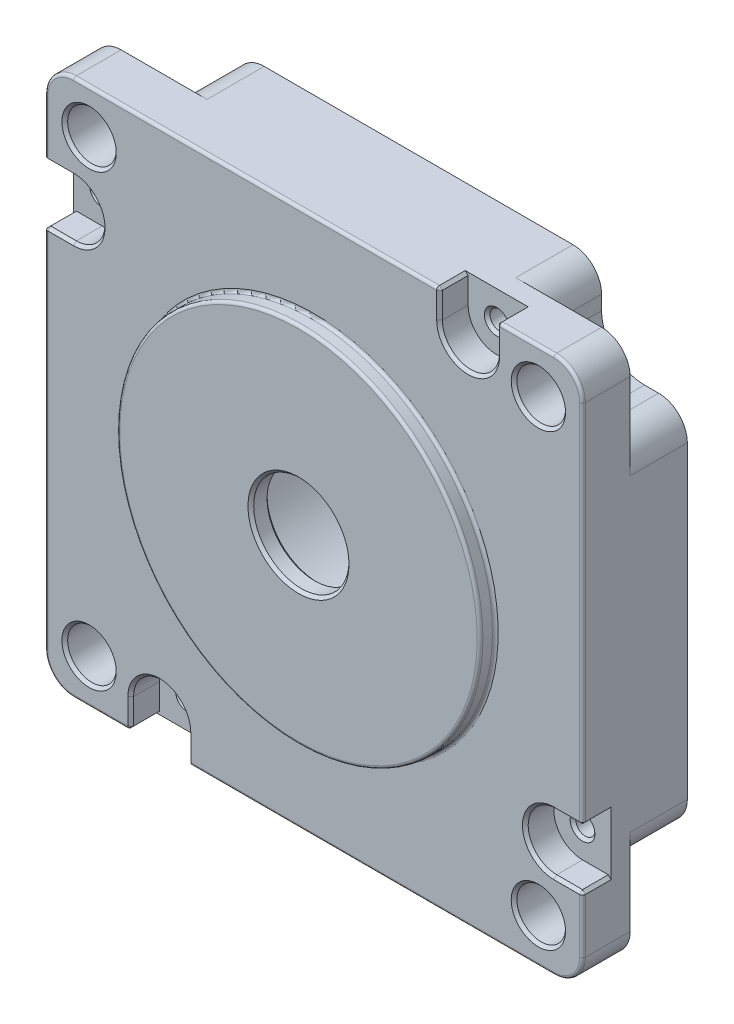
SolidWorks part; units mm, degrees
material "1060 Alloy"
ref_plane "Front Plane" through (0, 0, 0) normal (0, 0, 1) x (1, 0, 0)
ref_plane "Top Plane" through (0, 0, 0) normal (0, 1, 0) x (1, 0, 0)
ref_plane "Right Plane" through (0, 0, 0) normal (1, 0, 0) x (0, 0, -1)
sketch "Sketch1" plane through (0, 0, 0) normal (0, 0, 1) x (1, 0, 0)
  line L0 (0, 28.2) -> (0, -28.2) construction
  line L1 (-28.2, 28.2) -> (28.2, 28.2) construction
  line L2 (-28.2, 28.2) -> (-28.2, -28.2) construction
  line L3 (-28.2, -28.2) -> (28.2, -28.2) construction
  line L4 (28.2, 28.2) -> (28.2, -28.2) construction
  line L5 (-28.2, 28.2) -> (28.2, -28.2) construction
  line L6 (-28.2, -28.2) -> (28.2, 28.2) construction
  line L7 (-25.2, 25.2) -> (25.2, 25.2) construction
  line L8 (-25.2, 25.2) -> (-25.2, -25.2) construction
  line L9 (-25.2, -25.2) -> (25.2, -25.2) construction
  line L10 (25.2, 25.2) -> (25.2, -25.2) construction
  line L11 (-25.2, 25.2) -> (25.2, -25.2) construction
  line L12 (-25.2, -25.2) -> (25.2, 25.2) construction
  line L13 (-28.2, 0) -> (28.2, 0) construction
  line L15 (-25.2, 28.2) -> (25.2, 28.2)
  line L16 (-28.2, 25.2) -> (-28.2, -25.2)
  line L17 (-25.2, -28.2) -> (25.2, -28.2)
  line L18 (28.2, 25.2) -> (28.2, -25.2)
  line L19 (-23.57, 23.57) -> (23.57, 23.57) construction
  line L20 (-23.57, 23.57) -> (-23.57, -23.57) construction
  line L21 (-23.57, -23.57) -> (23.57, -23.57) construction
  line L22 (23.57, 23.57) -> (23.57, -23.57) construction
  line L23 (-23.57, 23.57) -> (23.57, -23.57) construction
  line L24 (-23.57, -23.57) -> (23.57, 23.57) construction
  line L25 (-24.2, -24.2) -> (24.2, -24.2) construction
  line L26 (-24.2, -24.2) -> (-24.2, 24.2) construction
  line L28 (24.2, -24.2) -> (24.2, 24.2) construction
  line L29 (-24.2, -24.2) -> (24.2, 24.2) construction
  line L30 (-24.2, 24.2) -> (24.2, -24.2) construction
  circle A0 centre (-25.2, 25.2) radius 3 construction
  circle A1 centre (25.2, 25.2) radius 3 construction
  circle A2 centre (25.2, -25.2) radius 3 construction
  circle A3 centre (-25.2, -25.2) radius 3 construction
  arc A4 (-25.2, 28.2) -> (-28.2, 25.2) centre (-25.2, 25.2) ccw
  circle A5 centre (0, 0) radius 5
  arc A6 (25.2, -28.2) -> (28.2, -25.2) centre (25.2, -25.2) ccw
  arc A7 (-25.2, -28.2) -> (-28.2, -25.2) centre (-25.2, -25.2) cw
  arc A8 (25.2, 28.2) -> (28.2, 25.2) centre (25.2, 25.2) cw
  circle A9 centre (-23.57, 23.57) radius 2.55
  circle A10 centre (23.57, 23.57) radius 2.55
  circle A11 centre (23.57, -23.57) radius 2.55
  circle A12 centre (-23.57, -23.57) radius 2.55
  circle A13 centre (16.2, 25.2) radius 1
  circle A15 centre (-25.2, 16.2) radius 1
  circle A17 centre (-16.2, -25.2) radius 1
  circle A18 centre (25.2, -16.2) radius 1
  point P0 (0, 0)
  point P6 (0, 0)
  dimension "D3" = 10
  dimension "D4" = 5.1
  dimension "D7" = 2
  dimension "D1" = 56.4
  dimension "D2" = 3
  dimension "D5" = 47.14
  dimension "D8" = 12
extrude "Boss-Extrude1" add sketch "Sketch1" along normal blind 11
sketch "Sketch2" plane through (0, 0, 11) normal (0, 0, 1) x (1, 0, 0)
  circle A0 centre (0, 0) radius 5
  circle A1 centre (0, 0) radius 19.05
  dimension "D1" = 38.1
extrude "Boss-Extrude2" add sketch "Sketch2" along normal blind 1.6
sketch "Sketch3" plane through (0, 0, 11) normal (0, 0, 1) x (1, 0, 0)
  line L0 (0, 28.2) -> (0, -28.2) construction
  line L1 (-28.2, 28.2) -> (28.2, 28.2) construction
  line L2 (-28.2, 28.2) -> (-28.2, -28.2) construction
  line L3 (-28.2, -28.2) -> (28.2, -28.2) construction
  line L4 (28.2, 28.2) -> (28.2, -28.2) construction
  line L5 (-28.2, 28.2) -> (28.2, -28.2) construction
  line L6 (-28.2, -28.2) -> (28.2, 28.2) construction
  line L7 (19.2, 28.2) -> (13.2, 28.2) construction
  line L8 (19.2, 28.2) -> (19.2, 25.2) construction
  line L9 (19.2, 25.2) -> (13.2, 25.2) construction
  line L10 (13.2, 28.2) -> (13.2, 25.2) construction
  line L11 (13.2, 28.2) -> (19.2, 28.2)
  line L12 (13.2, 28.2) -> (13.2, 25.2)
  line L13 (-28.2, 0) -> (28.2, 0) construction
  line L14 (19.2, 28.2) -> (19.2, 25.2)
  line L18 (-28.2, 13.2) -> (-28.2, 19.2)
  line L19 (-28.2, 13.2) -> (-25.2, 13.2)
  line L20 (-28.2, 19.2) -> (-25.2, 19.2)
  line L21 (28.2, -13.2) -> (28.2, -19.2)
  line L22 (28.2, -13.2) -> (25.2, -13.2)
  line L23 (28.2, -19.2) -> (25.2, -19.2)
  line L27 (-13.2, -28.2) -> (-13.2, -25.2)
  line L28 (-13.2, -28.2) -> (-19.2, -28.2)
  line L29 (-19.2, -28.2) -> (-19.2, -25.2)
  circle A0 centre (16.2, 25.2) radius 3 construction
  arc A1 (13.2, 25.2) -> (19.2, 25.2) centre (16.2, 25.2) ccw
  arc A3 (-25.2, 13.2) -> (-25.2, 19.2) centre (-25.2, 16.2) ccw
  arc A4 (25.2, -13.2) -> (25.2, -19.2) centre (25.2, -16.2) ccw
  arc A6 (-13.2, -25.2) -> (-19.2, -25.2) centre (-16.2, -25.2) ccw
  point P0 (0, 0)
  dimension "D1" = 56.4
  dimension "D2" = 9
  dimension "D3" = 6
  dimension "D4" = 3
extrude "Cut-Extrude1" cut sketch "Sketch3" against normal blind 3
fillet "Fillet1" radius 0.3 14 edges at (-28.2, 22.2, 11) (-27.3213, 27.3213, 11) (22.2, 28.2, 11) (27.3213, 27.3213, 11) (28.2, -22.2, 11) (27.3213, -27.3213, 11) (-22.2, -28.2, 11) (-27.3213, -27.3213, 11) (-6, 28.2, 11) (28.2, 6, 11) (6, -28.2, 11) (-28.2, -6, 11) (-19.05, 0, 11) (19.05, 0, 12.6)
chamfer "Chamfer1" distance 0.3 angle 45 32 edges at (13.2, 28.2, 9.35) (19.2, 28.2, 9.35) (13.2, 28.1121, 10.9121) (19.2, 28.1121, 10.9121) (13.2, 26.55, 11) (19.2, 26.55, 11) (16.2, 22.2, 11) (-15.2, -25.2, 8) (26.2, -16.2, 8) (17.2, 25.2, 8) (-24.2, 16.2, 8) (-13.2, -28.2, 9.35) (-19.2, -28.2, 9.35) (-13.2, -28.1121, 10.9121) (-19.2, -28.1121, 10.9121) (-13.2, -26.55, 11) (-19.2, -26.55, 11) (-16.2, -22.2, 11) (28.2, -13.2, 9.35) (28.2, -19.2, 9.35) (28.1121, -13.2, 10.9121) (28.1121, -19.2, 10.9121) (26.55, -13.2, 11) (26.55, -19.2, 11) (22.2, -16.2, 11) (-28.2, 13.2, 9.35) (-28.2, 19.2, 9.35) (-28.1121, 13.2, 10.9121) (-28.1121, 19.2, 10.9121) (-26.55, 13.2, 11) (-26.55, 19.2, 11) (-22.2, 16.2, 11)
sketch "Sketch4" plane through (0, 0, 0) normal (0, 0, -1) x (-1, 0, 0)
  line L0 (0, 28.2) -> (0, -28.2) construction
  line L1 (-28.2, 28.2) -> (28.2, 28.2) construction
  line L2 (-28.2, 28.2) -> (-28.2, -28.2) construction
  line L3 (-28.2, -28.2) -> (28.2, -28.2) construction
  line L4 (28.2, 28.2) -> (28.2, -28.2) construction
  line L5 (-28.2, 28.2) -> (28.2, -28.2) construction
  line L6 (-28.2, -28.2) -> (28.2, 28.2) construction
  line L7 (-23.7, 23.7) -> (23.7, 23.7) construction
  line L8 (-23.7, 23.7) -> (-23.7, -23.7) construction
  line L9 (-23.7, -23.7) -> (23.7, -23.7) construction
  line L10 (23.7, 23.7) -> (23.7, -23.7) construction
  line L11 (-23.7, 23.7) -> (23.7, -23.7) construction
  line L12 (-23.7, -23.7) -> (23.7, 23.7) construction
  line L13 (-28.2, 0) -> (28.2, 0) construction
  line L14 (-23.7, 19.2) -> (-25.1852, 19.2)
  line L15 (-19.2, 23.7) -> (-19.2, 25.2)
  line L16 (-28.2, 16.2) -> (-28.2, 25.2)
  line L17 (-25.2, 28.2) -> (-16.2, 28.2)
  line L18 (19.2, 23.7) -> (19.2, 25.2)
  line L19 (23.7, 19.2) -> (25.1852, 19.2)
  line L20 (28.2, 16.2) -> (28.2, 25.2)
  line L21 (25.2, 28.2) -> (16.2, 28.2)
  line L22 (-28.2, -16.2) -> (-28.2, -25.2)
  line L23 (-23.7, -19.2) -> (-25.1852, -19.2)
  line L24 (-19.2, -23.7) -> (-19.2, -25.2)
  line L25 (-25.2, -28.2) -> (-16.2, -28.2)
  line L26 (28.2, -16.2) -> (28.2, -25.2)
  line L27 (23.7, -19.2) -> (25.1852, -19.2)
  line L28 (19.2, -23.7) -> (19.2, -25.2)
  line L29 (25.2, -28.2) -> (16.2, -28.2)
  arc A0 (-25.2, 28.2) -> (-28.2, 25.2) centre (-25.2, 25.2) ccw
  arc A1 (-16.2, 28.2) -> (-19.2, 25.2) centre (-16.2, 25.2) ccw
  arc A2 (-28.2, 16.2) -> (-25.1852, 19.2) centre (-25.2, 16.2) cw
  arc A3 (-23.7, 19.2) -> (-19.2, 23.7) centre (-23.7, 23.7) ccw
  arc A4 (23.7, 19.2) -> (19.2, 23.7) centre (23.7, 23.7) cw
  arc A5 (28.2, 16.2) -> (25.1852, 19.2) centre (25.2, 16.2) ccw
  arc A6 (25.2, 28.2) -> (28.2, 25.2) centre (25.2, 25.2) cw
  arc A7 (16.2, 28.2) -> (19.2, 25.2) centre (16.2, 25.2) cw
  arc A8 (-25.2, -28.2) -> (-28.2, -25.2) centre (-25.2, -25.2) cw
  arc A9 (-28.2, -16.2) -> (-25.1852, -19.2) centre (-25.2, -16.2) ccw
  arc A10 (-23.7, -19.2) -> (-19.2, -23.7) centre (-23.7, -23.7) cw
  arc A11 (-16.2, -28.2) -> (-19.2, -25.2) centre (-16.2, -25.2) cw
  arc A12 (25.2, -28.2) -> (28.2, -25.2) centre (25.2, -25.2) ccw
  arc A13 (28.2, -16.2) -> (25.1852, -19.2) centre (25.2, -16.2) cw
  arc A14 (23.7, -19.2) -> (19.2, -23.7) centre (23.7, -23.7) ccw
  arc A15 (16.2, -28.2) -> (19.2, -25.2) centre (16.2, -25.2) ccw
  point P0 (0, 0)
  point P6 (0, 0)
  dimension "D3" = 6
  dimension "D1" = 56.4
  dimension "D2" = 47.4
extrude "Cut-Extrude2" cut sketch "Sketch4" against normal blind 6
chamfer "Chamfer2" distance 0.3 angle 45 8 edges at (-26.12, -23.57, 11) (-26.12, -23.57, 6) (26.12, -23.57, 6) (26.12, -23.57, 11) (21.02, 23.57, 6) (21.02, 23.57, 11) (-21.02, 23.57, 6) (-21.02, 23.57, 11)
sketch "Sketch5" plane through (0, 0, 0) normal (0, 0, -1) x (-1, 0, 0)
  line L1 (16.2, -28.2) -> (-16.2, -28.2) construction
  line L2 (10.811, -26.1) -> (26.1, -10.811)
  line L3 (26.1, -10.811) -> (26.1, 10.811)
  line L4 (26.1, 10.811) -> (10.811, 26.1)
  line L5 (10.811, 26.1) -> (-10.811, 26.1)
  line L6 (-10.811, 26.1) -> (-26.1, 10.811)
  line L7 (-26.1, 10.811) -> (-26.1, -10.811)
  line L8 (-26.1, -10.811) -> (-10.811, -26.1)
  line L9 (-10.811, -26.1) -> (10.811, -26.1)
  circle A0 centre (0, 0) radius 26.1 construction
  dimension "D1" = 52.2
extrude "Cut-Extrude3" cut sketch "Sketch5" against normal blind 8
sketch "Sketch6" plane through (0, 0, 8) normal (0, 0, -1) x (-1, 0, 0)
  circle A0 centre (0, 0) radius 5
  circle A1 centre (0, 0) radius 9
  dimension "D1" = 18
extrude "Cut-Extrude4" cut sketch "Sketch6" against normal blind 2.6
sketch "Sketch7" plane through (0, 0, 8) normal (0, 0, -1) x (-1, 0, 0)
  circle A0 centre (0, 0) radius 9
  circle A1 centre (0, 0) radius 11
  dimension "D1" = 22
extrude "Cut-Extrude5" cut sketch "Sketch7" against normal blind 1.6
sketch "Sketch8" plane through (0, 0, 8) normal (0, 0, -1) x (-1, 0, 0)
  circle A0 centre (0, 0) radius 11
  circle A1 centre (0, 0) radius 17.5
  dimension "D1" = 35
extrude "Boss-Extrude3" add sketch "Sketch8" along normal blind 3
sketch "Sketch9" plane through (0, 0, 5) normal (0, 0, -1) x (-1, 0, 0)
  circle A0 centre (0, 0) radius 11
  circle A1 centre (0, 0) radius 17
  dimension "D1" = 34
extrude "Boss-Extrude4" add sketch "Sketch9" along normal blind 7
chamfer "Chamfer3" distance 0.3 angle 45 14 edges at (-15.2, -25.2, 0) (-24.2, 16.2, 0) (17.2, 25.2, 0) (26.2, -16.2, 0) (26.1, 0, 0) (18.4555, -18.4555, 0) (0, -26.1, 0) (-18.4555, -18.4555, 0) (-26.1, 0, 0) (-18.4555, 18.4555, 0) (0, 26.1, 0) (18.4555, 18.4555, 0) (-5, 0, 10.6) (5, 0, 12.6)
chamfer "Chamfer4" distance 0.5 angle 45 1 edges at (-17, 0, -2)
chamfer "Chamfer5" distance 1 angle 60 1 edges at (-11, 0, -2) first distance on face at (-16.5, 0, -2)
